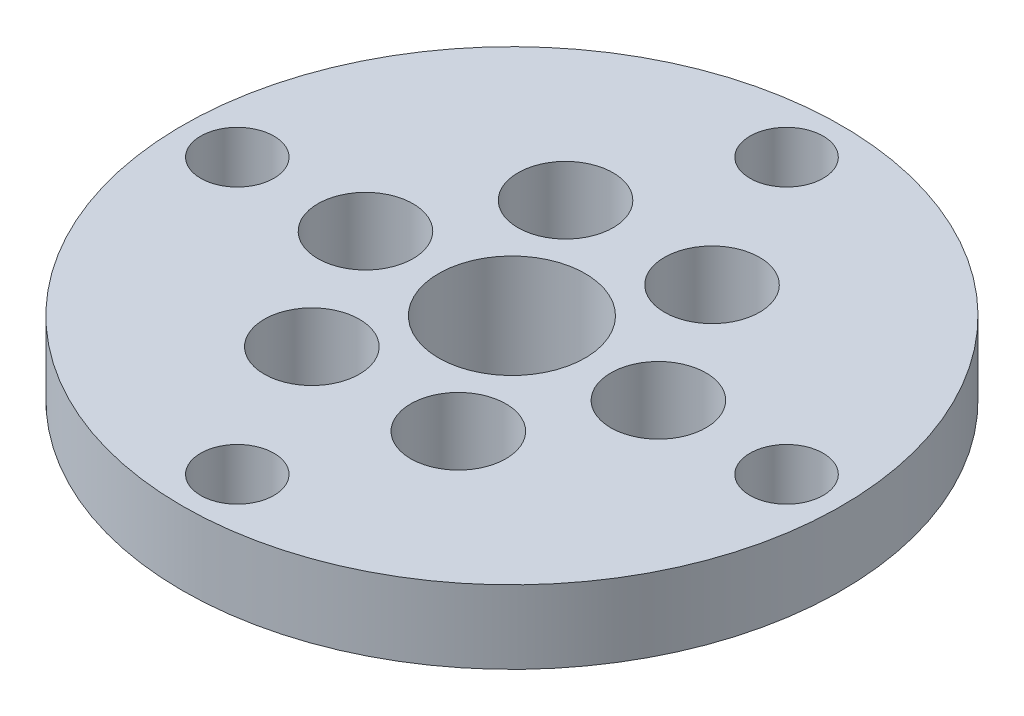
SolidWorks part; units mm, degrees
material "6061-T6 (SS)"
ref_plane "Front Plane" through (0, 0, 0) normal (0, 0, 1) x (1, 0, 0)
ref_plane "Top Plane" through (0, 0, 0) normal (0, 1, 0) x (1, 0, 0)
ref_plane "Right Plane" through (0, 0, 0) normal (1, 0, 0) x (0, 0, -1)
sketch "Sketch1" plane through (0, 0, 0) normal (0, 1, 0) x (1, 0, 0)
  circle A0 centre (0, 0) radius 15
  dimension "D1" = 30
extrude "Boss-Extrude1" add sketch "Sketch1" along normal blind 5
sketch "Sketch2" plane through (0, 0, 0) normal (0, 1, 0) x (1, 0, 0)
  circle A0 centre (0, 0) radius 13.5 construction
  circle A1 centre (-5, 8.6603) radius 1.25
  circle A2 centre (5, 8.6603) radius 1.25
  circle A3 centre (10, 0) radius 1.25
  circle A4 centre (5, -8.6603) radius 1.25
  circle A5 centre (-5, -8.6603) radius 1.25
  circle A6 centre (-10, 0) radius 1.25
  circle A7 centre (0, 0) radius 10 construction
  circle A8 centre (0, 0) radius 5
  point P3 (-10, 0)
  point P4 (-5, 8.6603)
  point P5 (5, 8.6603)
  point P6 (10, 0)
  point P7 (5, -8.6603)
  point P8 (-5, -8.6603)
  point P23 (0, 0)
  dimension "D1" = 27
  dimension "D2" = 2.5
  dimension "D4" = 20
  dimension "D5" = 10
  dimension "D3" = 6
sketch "Sketch3" plane through (0, 5, 0) normal (0, 1, 0) x (1, 0, 0)
  circle A0 centre (0, 0) radius 22.5
  dimension "D1" = 45
extrude "Boss-Extrude3" add sketch "Sketch3" along normal blind 5
extrude "Cut-Extrude1" cut sketch "Sketch2" along normal blind 11.5
sketch "Sketch4" plane through (0, 10, 0) normal (0, 1, 0) x (1, 0, 0)
  circle A1 centre (10, 0) radius 3.25
  circle A2 centre (5, 8.6603) radius 3.25
  circle A3 centre (5, 8.6603) radius 3.25
  circle A4 centre (5, -8.6603) radius 3.25
  circle A5 centre (-5, -8.6603) radius 3.25
  circle A6 centre (-10, 0) radius 3.25
  circle A7 centre (-5, 8.6603) radius 3.25
  point P15 (0, 0)
  dimension "D1" = 2
  dimension "D2" = 6
extrude "Cut-Extrude2" cut sketch "Sketch4" against normal offset from surface (6 mm away) 4 up to face at (5, 0, 9.9103)
sketch "Sketch5" plane through (0, 10, 0) normal (0, 1, 0) x (1, 0, 0)
  line L0 (0, 0) -> (0, 18.75) construction
  circle A0 centre (0, 0) radius 18.75 construction
  circle A1 centre (0, 18.75) radius 2.5
  circle A2 centre (18.75, 0) radius 2.5
  circle A3 centre (0, -18.75) radius 2.5
  circle A4 centre (-18.75, 0) radius 2.5
  point P14 (0, 0)
  dimension "D1" = 37.5
  dimension "D2" = 5
  dimension "D3" = 4
extrude "Cut-Extrude3" cut sketch "Sketch5" against normal offset from surface (6.5 mm away) 3.5 up to face at (5, 0, 9.9103)
